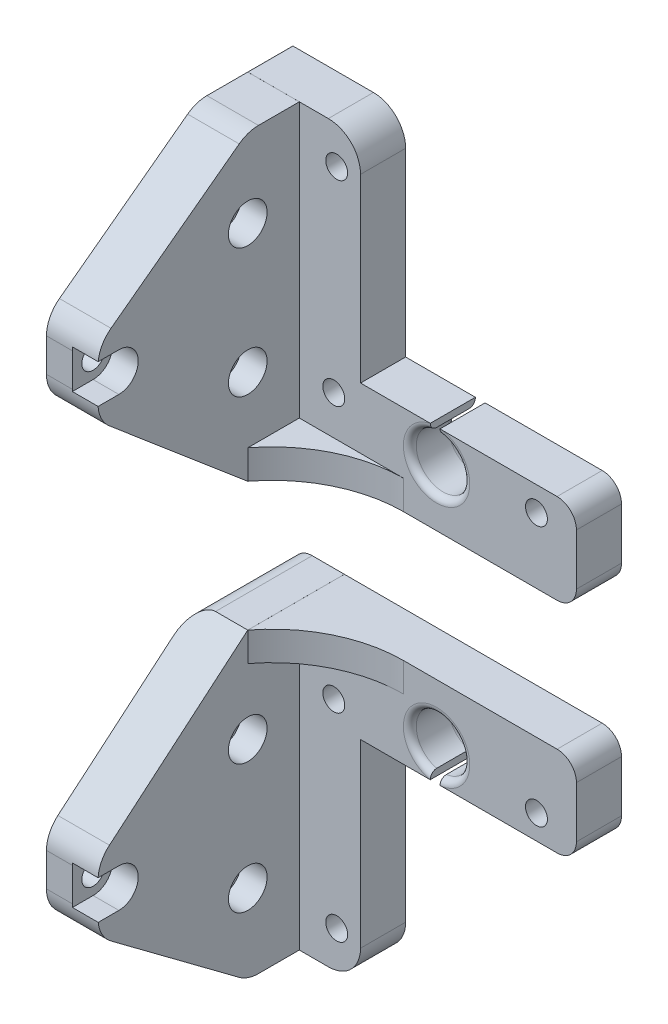
SolidWorks part; units mm, degrees
material "ABS"
ref_plane "Front Plane" through (0, 0, 0) normal (0, 0, 1) x (1, 0, 0)
ref_plane "Top Plane" through (0, 0, 0) normal (0, 1, 0) x (1, 0, 0)
ref_plane "Right Plane" through (0, 0, 0) normal (1, 0, 0) x (0, 0, -1)
ref_plane "Plane5" through (60, 0, 0) normal (1, 0, 0) x (0, 0, -1)
sketch "Sketch50" plane through (60, 0, 0) normal (1, 0, 0) x (0, 0, -1)
  line L0 (-38.2349, -28) -> (-38.2349, -38)
  line L1 (0, -55.3249) -> (-15, -55.3249)
  line L2 (0, -8.3249) -> (-15, -8.3249)
  line L4 (0, -55.3249) -> (0, -8.3249)
  line L5 (-15, -2.0171) -> (-15, -57.8143) construction
  line L9 (-38.2349, -28) -> (-15, -8.3249)
  line L10 (-38.2349, -38) -> (-15, -55.3249)
  circle A0 centre (-35, -33) radius 1.75
  circle A1 centre (-15, -23) radius 1.75
  circle A2 centre (-15, -43) radius 1.75
  dimension "D1" = 3.5
  dimension "D2" = 3.5
  dimension "D3" = 3.5
  dimension "D4" = 20
  dimension "D5" = 20
  dimension "D6" = 47
  dimension "D7" = 15
  dimension "D8" = 10
extrude "Extrude1" add sketch "Sketch50" along normal blind 8 separate body
sketch "Sketch52" plane through (0, 0, 0) normal (0, 0, -1) x (-1, 0, 0)
  line L0 (-60.0211, -55.3284) -> (-60.0211, -8.3284)
  line L1 (-111, -8.3284) -> (-111, -22.2806)
  line L2 (-60.0211, -8.3284) -> (-111, -8.3284)
  line L3 (-77.5, -22.2806) -> (-111, -22.2806)
  line L4 (-60.0211, -55.3284) -> (-77.5, -55.3284)
  line L5 (-77.5, -55.3249) -> (-77.5, -8.3249)
  line L6 (-77.5, -55.3284) -> (-77.5, -22.2806)
  circle A0 centre (-89.3, -17.2) radius 4.15
  circle A1 centre (-73.3515, -18.9313) radius 1.7
  circle A2 centre (-104.8, -18.5) radius 1.7
  circle A3 centre (-73.8015, -49.5086) radius 1.7
  point P3 (-113, -87.5802)
  point P9 (-74.0211, -54.9585)
  point P10 (-74.0211, -7.7617)
  dimension "D2" = 47
  dimension "D4" = 3.4
  dimension "D3" = 8.3
  dimension "D1" = 9.5
extrude "Extrude2" add sketch "Sketch52" against normal blind 7
fillet "Fillet1" radius 3 2 edges at (111, -22.2806, 3.5) (111, -8.3284, 3.5)
fillet "Fillet2" radius 5 1 edges at (77.5, -55.3284, 3.5)
sketch "Sketch54" plane through (0, -8.3284, 0) normal (0, 1, 0) x (1, 0, 0)
  line L0 (68, -7) -> (108, -7) construction
  line L1 (68, -15) -> (68, -7)
  line L2 (68, -15) -> (68, -38.2349) construction
  line L3 (68, 0) -> (68, -15) construction
  line L4 (68, -7) -> (84.1795, -7)
  arc A0 (84.1795, -7) -> (68, -15) centre (84.1795, -27.3609) ccw
extrude "Extrude3" add sketch "Sketch54" against normal blind 4.5
fillet "Fillet4" radius 5 3 edges at (64, -28, 38.2349) (64, -38, 38.2349) (64, -55.3249, 15)
fillet "Fillet5" radius 3 1 edges at (60, -8.3249, 7.5)
sketch "Sketch55" plane through (68, 0, 0) normal (1, 0, 0) x (0, 0, -1)
  line L0 (-35, -30) -> (-38.7879, -30)
  line L1 (-38.7879, -30) -> (-38.7879, -36)
  line L2 (-35, -36) -> (-38.7879, -36)
  arc A0 (-35, -36) -> (-35, -30) centre (-35, -33) ccw
  circle A1 centre (-15, -23) radius 3
  circle A2 centre (-15, -43) radius 3
  dimension "D1" = 6
  dimension "D2" = 6
  dimension "D3" = 6
extrude "Cut-Extrude3" cut sketch "Sketch55" against normal blind 4
sketch "Sketch56" plane through (0, 0, 0) normal (0, 0, -1) x (-1, 0, 0)
  line L0 (-108, -22.2806) -> (-77.5, -22.2806) construction
  line L1 (-89.3173, -23.6005) -> (-88.3204, -23.6005)
  line L2 (-89.3173, -23.6005) -> (-89.3173, -20.9607)
  line L3 (-89.3173, -20.9607) -> (-88.3204, -20.9607)
  line L4 (-88.3204, -23.6005) -> (-88.3204, -20.9607)
  line L5 (-89.3173, -23.6005) -> (-88.3204, -20.9607) construction
  line L6 (-89.3173, -20.9607) -> (-88.3204, -23.6005) construction
  point P0 (-88.8189, -22.2806)
fillet "Fillet9" radius 1 1 edges at (89.3, -13.05, 0)
fillet "Fillet10" radius 1 1 edges at (89.3, -13.05, 7)
sketch "Sketch57" plane through (0, -22.2806, 0) normal (0, -1, 0) x (1, 0, 0)
  line L0 (88.8276, 7.5275) -> (89.8276, 7.5275)
  line L2 (89.8276, -0.6284) -> (89.8276, 7.5275)
  line L3 (88.8276, -0.6284) -> (88.8276, 7.5275)
  line L4 (88.8276, -0.6284) -> (89.8276, -0.6284)
extrude "Extrude4" cut sketch "Sketch57" against normal blind 4
ref_plane "Plane6" through (0, 1.6716, 0) normal (0, 1, 0) x (1, 0, 0)
extrude "Cut-Extrude4" cut sketch "Sketch56" against normal up to surface (7 mm away) up to face at (84.7186, -28.299, 7)
mirror "Mirror7" about plane through (0, 1.6716, 0) normal (0, 1, 0) of bodies 133
